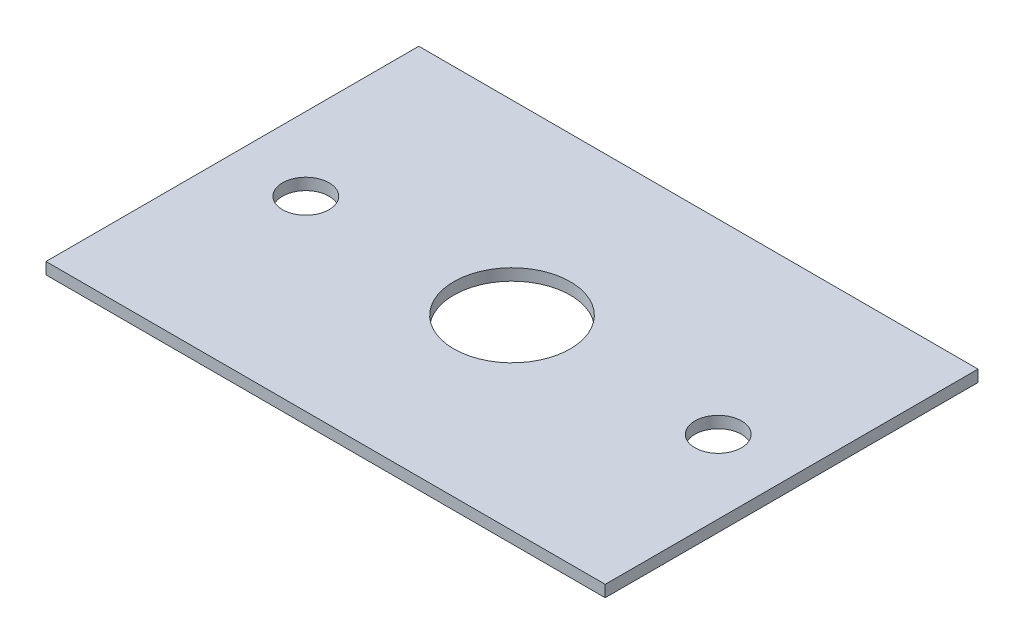
SolidWorks part; units mm, degrees
material "1023 Carbon Steel Sheet (SS)"
ref_plane "Front Plane" through (0, 0, 0) normal (0, 0, 1) x (1, 0, 0)
ref_plane "Top Plane" through (0, 0, 0) normal (0, 1, 0) x (1, 0, 0)
ref_plane "Right Plane" through (0, 0, 0) normal (1, 0, 0) x (0, 0, -1)
sketch "Sketch1" plane through (0, 0, 0) normal (0, 1, 0) x (1, 0, 0)
  line L1 (38.1, -25.4) -> (-38.1, -25.4)
  line L2 (38.1, -25.4) -> (38.1, 25.4)
  line L3 (38.1, 25.4) -> (-38.1, 25.4)
  line L4 (-38.1, -25.4) -> (-38.1, 25.4)
  line L5 (38.1, -25.4) -> (-38.1, 25.4) construction
  line L6 (38.1, 25.4) -> (-38.1, -25.4) construction
  circle A0 centre (0, 0) radius 7.9375
  circle A1 centre (-28.1, 0) radius 3.175
  circle A2 centre (28.1, 0) radius 3.175
  point P0 (0, 0)
  dimension "D3" = 15.875
  dimension "D6" = 6.35
  dimension "D7" = 6.35
  dimension "D1" = 50.8
  dimension "D2" = 76.2
  dimension "D4" = 10
  dimension "D5" = 10
extrude "Boss-Extrude1" add sketch "Sketch1" along normal blind 1.5875
equation "\"D7@Sketch1\"=\"D6@Sketch1\""
equation "\"D4@Sketch1\"=\"D5@Sketch1\""
